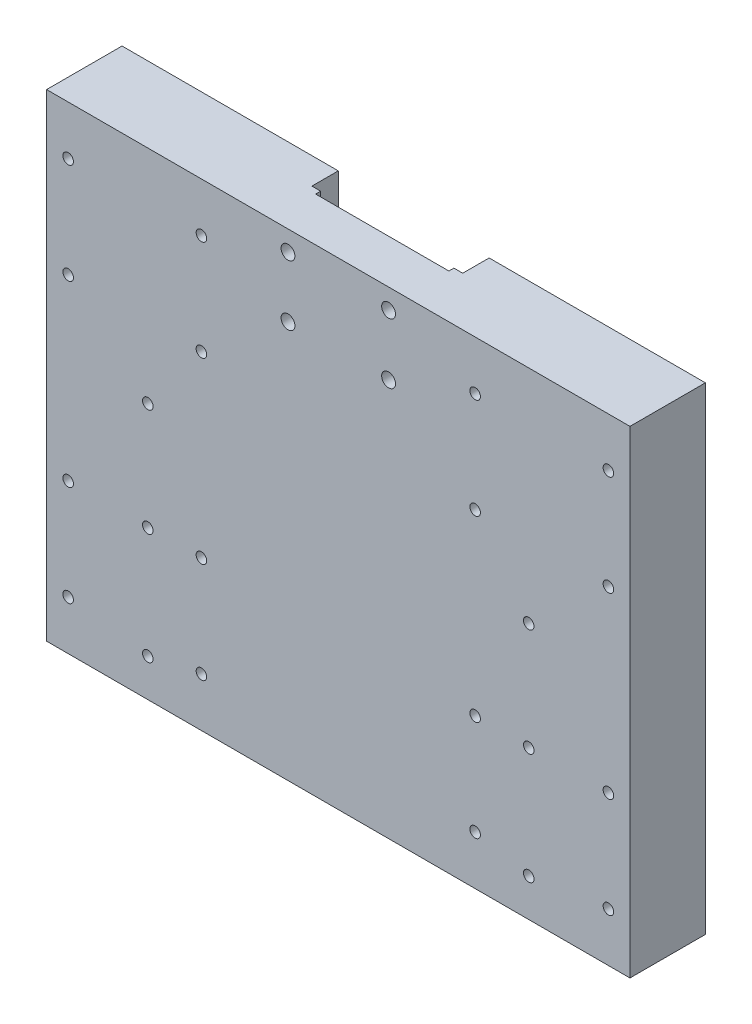
SolidWorks part; units mm, degrees
ref_plane "Piano frontale" through (0, 0, 0) normal (0, 0, 1) x (1, 0, 0)
ref_plane "Piano superiore" through (0, 0, 0) normal (0, 1, 0) x (1, 0, 0)
ref_plane "Piano destro" through (0, 0, 0) normal (1, 0, 0) x (0, 0, -1)
sketch "Schizzo1" plane through (0, 0, 0) normal (0, 0, 1) x (1, 0, 0)
  line L1 (116, -95) -> (-116, -95)
  line L2 (116, -95) -> (116, 95)
  line L3 (116, 95) -> (-116, 95)
  line L4 (-116, -95) -> (-116, 95)
  line L5 (116, -95) -> (-116, 95) construction
  line L6 (116, 95) -> (-116, -95) construction
  point P0 (0, 0)
  dimension "D1" = 232
  dimension "D2" = 190
extrude "Estrusione-Estrusione1" add sketch "Schizzo1" along normal blind 30
sketch "Schizzo3" plane through (0, 0, 30) normal (0, 0, 1) x (1, 0, 0)
  line L0 (20, 7) -> (-20, 7) construction
  line L1 (-20, 7) -> (20, -17) construction
  line L2 (20, -17) -> (20, 7) construction
  line L3 (20, 7) -> (-20, -17) construction
  line L4 (-20, -17) -> (-20, 7) construction
  line L5 (-20, -17) -> (20, -17) construction
  circle A8 centre (20, 7) radius 3
  circle A9 centre (-20, 7) radius 3
  circle A10 centre (-20, -17) radius 3
  circle A11 centre (20, -17) radius 3
  point P21 (0, -5)
  dimension "D1" = 40
  dimension "D2" = 24
sketch "Schizzo4" plane through (0, 95, 0) normal (0, 1, 0) x (1, 0, 0)
  line L0 (116, 0) -> (-116, 0) construction
  line L1 (30, 0) -> (-30, 0)
  line L2 (30, 0) -> (30, -10.5)
  line L3 (30, -10.5) -> (-30, -10.5)
  line L4 (-30, 0) -> (-30, -10.5)
  dimension "D1" = 10.5
extrude "Taglio-Estrusione2" cut sketch "Schizzo4" against normal through all
sketch "Sketch1" plane through (0, 0, 0) normal (0, 0, -1) x (-1, 0, 0)
  line L0 (-52.5, 88.5) -> (-109.5, 88.5) construction
  line L1 (-81, 88.5) -> (-80, -95) construction
  point P0 (-109.5, 88.5)
  point P1 (-109.5, 43.5)
  point P3 (-52.5, 88.5)
  point P5 (-52.5, 43.5)
  point P7 (-52.5, -43.5)
  point P9 (-109.5, -43.5)
  point P11 (-109.5, -88.5)
  point P13 (-52.5, -88.5)
  point P15 (52.5, -88.5)
  point P17 (109.5, -88.5)
  point P19 (109.5, -43.5)
  point P21 (52.5, -43.5)
  point P23 (52.5, 43.5)
  point P25 (109.5, 43.5)
  point P27 (109.5, 88.5)
  point P29 (52.5, 88.5)
hole_wizard "Tap Drill for M5 Tap1" positions "Sketch2" profile "Sketch3" hole size "M5" standard "ISO" end condition through all
sketch "Sketch2" plane through (0, 0, 0) normal (0, 0, -1) x (-1, 0, 0)
  line L3 (0, 95) -> (0, -95) construction
  line L4 (-116, 95) -> (116, 95) construction
  line L5 (116, -95) -> (-116, -95) construction
  line L7 (116, 0) -> (-116, 0) construction
  line L8 (116, 95) -> (116, -95) construction
  line L9 (-116, -95) -> (-116, 95) construction
  line L13 (-54.4288, 75.5) -> (-107.4288, 75.5)
  line L14 (-54.4288, 75.5) -> (-54.4288, 35.5)
  line L15 (-54.4288, 35.5) -> (-107.4288, 35.5)
  line L16 (-107.4288, 75.5) -> (-107.4288, 35.5)
  line L18 (-107.4288, -35.5) -> (-54.4288, -35.5)
  line L19 (-107.4288, -35.5) -> (-107.4288, -75.5)
  line L20 (-107.4288, -75.5) -> (-54.4288, -75.5)
  line L21 (-54.4288, -35.5) -> (-54.4288, -75.5)
  point P72 (-54.4288, 75.5)
  point P76 (-107.4288, 35.5)
  point P681 (-107.4288, -75.5)
  point P682 (-107.4288, -35.5)
  point P683 (-54.4288, -35.5)
  point P684 (-54.4288, -75.5)
  point P685 (54.4288, -75.5)
  point P686 (54.4288, -35.5)
  point P687 (107.4288, -35.5)
  point P688 (107.4288, -75.5)
  point P689 (107.4288, 75.5)
  point P690 (107.4288, 35.5)
  point P691 (54.4288, 35.5)
  point P692 (54.4288, 75.5)
  point P695 (-107.4288, 75.5)
  point P699 (-54.4288, 35.5)
  point P899 (0, 0)
  point P900 (0, 0)
  dimension "D1" = 53
  dimension "D2" = 40
sketch "Sketch3" plane through (54.4288, 35.5, 0) normal (1, 0, 0) x (0, 1, 0)
  line L0 (0, 0) -> (0, 30)
  line L1 (0, 30) -> (2.1, 30)
  line L2 (2.1, 30) -> (2.1, 0)
  line L5 (2.1, 0) -> (0, 0)
  line L11 (0, -6.35) -> (0, 107.95) construction
  dimension "Thru Hole Dia." = 4.2
  dimension "Thru Hole Depth" = 30
hole_wizard "M5 Clearance Hole1" positions "Sketch4" profile "Sketch5" hole size "M5" standard "ISO" end condition through all
sketch "Sketch4" plane through (0, 0, 30) normal (0, 0, 1) x (1, 0, 0)
  point P0 (-20, 87)
  point P3 (20, 87)
  point P6 (20, 63)
  point P9 (-20, 63)
sketch "Sketch5" plane through (-20, 87, 30) normal (1, 0, 0) x (0, -1, 0)
  line L0 (0, 0) -> (0, 30)
  line L1 (0, 30) -> (2.75, 30)
  line L2 (2.75, 30) -> (2.75, 0)
  line L5 (2.75, 0) -> (0, 0)
  line L11 (0, -6.35) -> (0, 107.95) construction
  dimension "Thru Hole Dia." = 5.5
  dimension "Thru Hole Depth" = 30
hole_wizard "Tap Drill for M5 Tap3" positions "Sketch6" profile "Sketch7" hole size "M5" standard "ISO" end condition up to next
sketch "Sketch6" plane through (0, 0, 30) normal (0, 0, 1) x (1, 0, 0)
  point P0 (-75.75, 7)
  point P6 (-75.75, -80)
  point P8 (75.75, 7)
  point P14 (75.75, -80)
  point P23 (-75.75, -35.7925)
  point P25 (75.75, -35.7925)
sketch "Sketch7" plane through (-75.75, 7, 30) normal (1, 0, 0) x (0, -1, 0)
  line L0 (0, 0) -> (0, 30)
  line L1 (0, 30) -> (2.1, 30)
  line L2 (2.1, 30) -> (2.1, 0)
  line L5 (2.1, 0) -> (0, 0)
  line L11 (0, -6.35) -> (0, 107.95) construction
  dimension "Thru Hole Dia." = 4.2
  dimension "Thru Hole Depth" = 30
sketch "Sketch8" plane through (0, 0, 10.5) normal (0, 0, -1) x (-1, 0, 0)
  line L0 (30, 95) -> (-30, 95) construction
  line L1 (-26.5, 95) -> (26.5, 95)
  line L2 (-26.5, 95) -> (-26.5, 43)
  line L3 (-26.5, 43) -> (26.5, 43)
  line L4 (26.5, 95) -> (26.5, 43)
  line L5 (-30, 78.9991) -> (30, 78.9991) construction
  line L6 (-30, -95) -> (-30, 95) construction
  line L7 (30, -95) -> (30, 95) construction
  line L8 (0, 78.9991) -> (0, 101.437) construction
  dimension "D1" = 26.5
  dimension "D2" = 26.5
  dimension "D3" = 52
extrude "Cut-Extrude1" cut sketch "Sketch8" against normal blind 2
